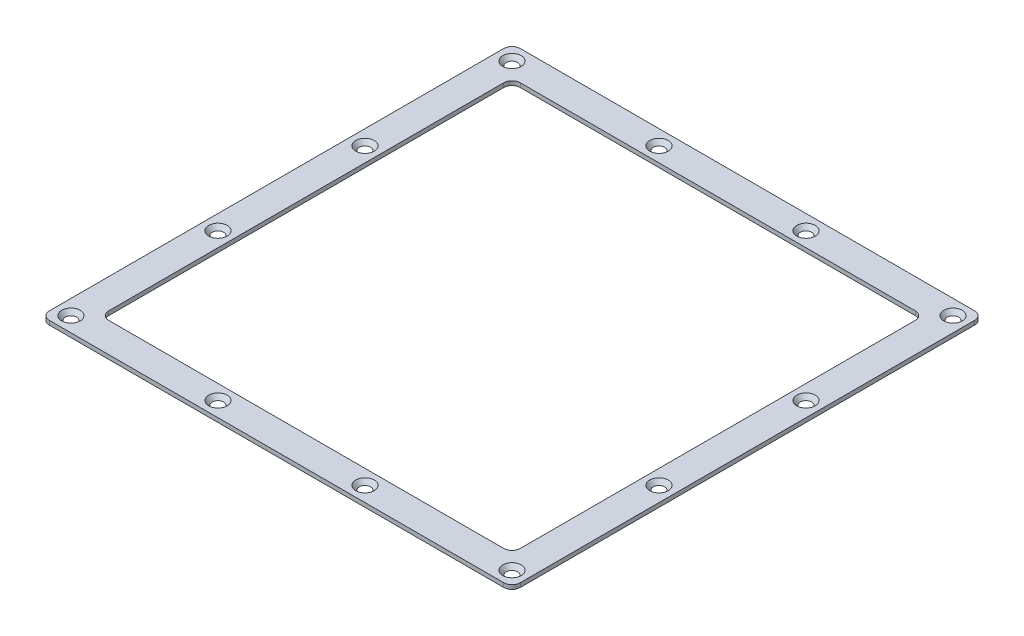
SolidWorks part; units mm, degrees
note: The reader was unsure of these and kept them because the rebuilt part matched: thickness of "Base-Flange1", "Sheet-Metal1", "Sheet-Metal2", "Sheet-Metal5".
material "6061 Alloy"
ref_plane "Front Plane" through (0, 0, 0) normal (0, 0, 1) x (1, 0, 0)
ref_plane "Top Plane" through (0, 0, 0) normal (0, 1, 0) x (1, 0, 0)
ref_plane "Right Plane" through (0, 0, 0) normal (1, 0, 0) x (0, 0, -1)
sketch "Sketch2" plane through (0, 0, 0) normal (0, 1, 0) x (1, 0, 0)
  line L1 (3.175, 0) -> (177.038, 0)
  line L2 (0, 3.175) -> (0, 177.038)
  line L3 (3.175, 180.213) -> (177.038, 180.213)
  line L4 (180.213, 3.175) -> (180.213, 177.038)
  arc A0 (180.213, 3.175) -> (177.038, 0) centre (177.038, 3.175) cw
  arc A1 (180.213, 177.038) -> (177.038, 180.213) centre (177.038, 177.038) ccw
  arc A2 (3.175, 180.213) -> (0, 177.038) centre (3.175, 177.038) ccw
  arc A3 (3.175, 0) -> (0, 3.175) centre (3.175, 3.175) cw
  point P9 (180.213, 180.213)
  point P12 (0, 180.213)
  point P15 (0, 0)
  dimension "D3" = 3.175
  dimension "D1" = 180.213
  dimension "D2" = 180.213
base flange "Base-Flange1" sketch "Sketch2" thickness 1.5875 reverse thickness direction no parameters "D1"=1.5875
sketch "Sketch7" plane through (0, 0, 0) normal (0, 1, 0) x (1, 0, 0)
  line L0 (0, 177.038) -> (0, 3.175) construction
  line L1 (14.5288, 168.8592) -> (165.6842, 168.8592)
  line L2 (11.3538, 165.6842) -> (11.3538, 14.5288)
  line L3 (14.5288, 11.3538) -> (165.6842, 11.3538)
  line L4 (168.8592, 165.6842) -> (168.8592, 14.5288)
  line L5 (177.038, 180.213) -> (3.175, 180.213) construction
  line L6 (180.213, 3.175) -> (180.213, 177.038) construction
  line L7 (3.175, 0) -> (177.038, 0) construction
  arc A0 (14.5288, 168.8592) -> (11.3538, 165.6842) centre (14.5288, 165.6842) ccw
  arc A1 (165.6842, 168.8592) -> (168.8592, 165.6842) centre (165.6842, 165.6842) cw
  arc A2 (165.6842, 11.3538) -> (168.8592, 14.5288) centre (165.6842, 14.5288) ccw
  arc A3 (11.3538, 14.5288) -> (14.5288, 11.3538) centre (14.5288, 14.5288) ccw
  point P10 (11.3538, 168.8592)
  point P13 (168.8592, 168.8592)
  point P18 (11.3538, 11.3538)
  dimension "D2" = 3.175
  dimension "D1" = 11.3538
  dimension ".45" = 11.3538
  dimension "D3" = 11.3538
  dimension "D4" = 11.3538
extrude "Cut-Extrude1" cut sketch "Sketch7" against normal through all normal cut yes
hole_wizard "CSK for #6 Flat Head Machine Screw1" positions "Sketch9" profile "Sketch8" countersink size "#6" standard "ANSI Inch" end condition through all
sketch "Sketch9" plane through (0, 0, 0) normal (0, 1, 0) x (1, 0, 0)
  line L2 (5.715, 174.4979) -> (180.213, 174.4979) construction
  line L3 (180.213, 3.175) -> (180.213, 177.038) construction
  line L4 (180.213, 174.4979) -> (5.715, 174.4979) construction
  line L5 (5.715, 174.4979) -> (5.715, 0) construction
  line L6 (3.175, 0) -> (177.038, 0) construction
  line L10 (11.3538, 11.3538) -> (11.3538, 90.1065) construction
  line L11 (11.3538, 165.6842) -> (11.3538, 14.5288) construction
  line L14 (177.038, 180.213) -> (3.175, 180.213) construction
  line L16 (90.1065, 11.3538) -> (90.1065, 168.8592) construction
  line L17 (14.5288, 11.3538) -> (165.6842, 11.3538) construction
  line L18 (165.6842, 168.8592) -> (14.5288, 168.8592) construction
  line L23 (14.5288, 11.3538) -> (11.3538, 11.3538) construction
  line L24 (180.213, 5.7149) -> (0, 5.7149) construction
  line L25 (180.213, 3.175) -> (180.213, 177.038) construction
  line L26 (0, 177.038) -> (0, 3.175) construction
  point P0 (5.715, 174.4979)
  point P26 (61.976, 174.4979)
  point P63 (61.976, 5.7149)
  point P64 (5.715, 5.7149)
  point P65 (5.715, 61.9759)
  point P66 (5.715, 118.2369)
  point P99 (118.237, 174.4979)
  point P100 (174.498, 174.4979)
  point P101 (174.498, 118.2369)
  point P102 (174.498, 61.9759)
  point P104 (118.237, 5.7149)
  point P142 (174.498, 5.7149)
  dimension "D1" = 5.715
  dimension "D2" = 5.7151
  dimension "D3" = 56.261
  dimension "D4" = 56.261
  dimension "D5" = 56.261
  dimension "D6" = 56.261
  dimension "D7" = 56.261
sketch "Sketch8" plane through (5.715, 0, -174.4979) normal (1, 0, 0) x (0, 0, 1)
  line L0 (0, 0) -> (0, 1.5875)
  line L1 (0, 1.5875) -> (1.8288, 1.5875)
  line L2 (1.8288, 1.5875) -> (1.8288, 1.9723)
  line L3 (1.8288, 1.9723) -> (3.5433, 0)
  line L5 (3.5433, 0) -> (0, 0)
  line L6 (-1.8288, 1.9723) -> (-3.5433, 0) construction
  line L11 (0, -6.35) -> (0, 107.95) construction
  dimension "Thru Hole Dia." = 3.6576
  dimension "Thru Hole Depth" = 1.5875
  dimension "Near C'Sink Dia." = 7.0866
  dimension "Near C'Sink Angle" = 82
sketch "Bend-Lines1" [suppressed] plane through (0, 0, 0) normal (0, 1, 0) x (1, 0, 0)
sketch "Bounding-Box1" [suppressed] plane through (0, 0, 0) normal (0, 1, 0) x (1, 0, 0)
sheet metal parameters "Sheet-Metal1" thickness 1.5875 parameters "D1"=1.5875
flat pattern "Flat-Pattern1" [suppressed]
sketch "Bend-Lines2" plane through (0, 0, 0) normal (0, 1, 0) x (1, 0, 0)
sketch "Bounding-Box2" [suppressed] plane through (0, 0, 0) normal (0, 1, 0) x (1, 0, 0)
sheet metal parameters "Sheet-Metal2" thickness 1.5875 parameters "D1"=1.5875, "D7"=0.7937
flat pattern "Flat-Pattern1"
sketch "Bend-Lines2" plane through (0, 0, 0) normal (0, 1, 0) x (1, 0, 0)
sketch "Bounding-Box2" [suppressed] plane through (0, 0, 0) normal (0, 1, 0) x (1, 0, 0)
sheet metal parameters "Sheet-Metal5" thickness 1.5875 parameters "D1"=1.5875, "D7"=0.7937
flat pattern "Flat-Pattern1"
sketch "Bend-Lines2" plane through (0, 0, 0) normal (0, 1, 0) x (1, 0, 0)
sketch3d "Bounding-Box2" [suppressed]
  line L0 (-177.0126, -3.175, 0) -> (-177.0126, 177.0126, 0) construction
  line L1 (3.175, -3.175, 0) -> (3.175, 177.0126, 0) construction
  line L2 (-177.0126, -3.175, 0) -> (3.175, -3.175, 0) construction
  line L3 (-177.0126, 177.0126, 0) -> (3.175, 177.0126, 0) construction
